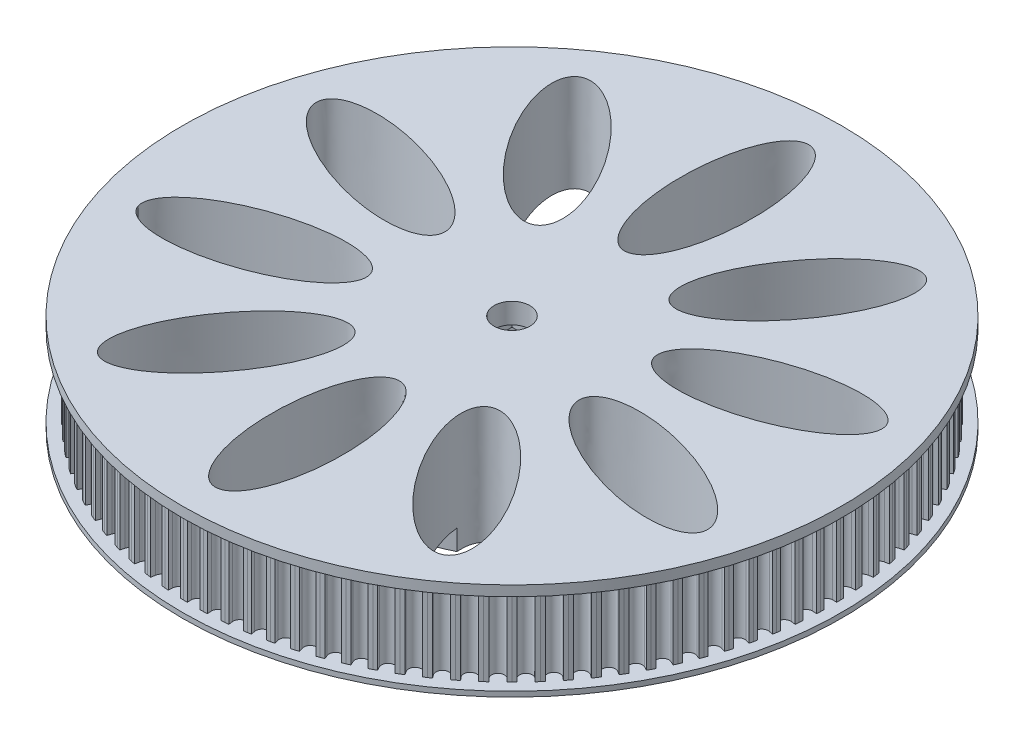
SolidWorks part; units mm, degrees
ref_plane "Front Plane" through (0, 0, 0) normal (0, 0, 1) x (1, 0, 0)
ref_plane "Top Plane" through (0, 0, 0) normal (0, 1, 0) x (1, 0, 0)
ref_plane "Right Plane" through (0, 0, 0) normal (1, 0, 0) x (0, 0, -1)
sketch "Sketch1" plane through (0, 0, 0) normal (0, 1, 0) x (1, 0, 0)
  circle A0 centre (0, 0) radius 32.2169
  circle A1 centre (0, 0) radius 8.55
  ellipse E0 centre (0, 20) end of major axis (0, 11) minor radius 3.5
  ellipse E1 centre (11.7557, 16.1803) end of major axis (6.4656, 8.8992) minor radius 3.5
  ellipse E2 centre (19.0211, 6.1803) end of major axis (27.5806, 8.9615) minor radius 3.5
  ellipse E3 centre (19.0211, -6.1803) end of major axis (10.4616, -3.3992) minor radius 3.5
  ellipse E4 centre (11.7557, -16.1803) end of major axis (17.0458, -23.4615) minor radius 3.5
  ellipse E5 centre (0, -20) end of major axis (0, -11) minor radius 3.5
  ellipse E6 centre (-11.7557, -16.1803) end of major axis (-6.4656, -8.8992) minor radius 3.5
  ellipse E7 centre (-19.0211, -6.1803) end of major axis (-27.5806, -8.9615) minor radius 3.5
  ellipse E8 centre (-19.0211, 6.1803) end of major axis (-27.5806, 8.9615) minor radius 3.5
  ellipse E9 centre (-11.7557, 16.1803) end of major axis (-17.0458, 23.4615) minor radius 3.5
  point P66 (0, 0)
  dimension "D1" = 64.4338
  dimension "D2" = 17.1
  dimension "D3" = 20
  dimension "D4" = 7
  dimension "D5" = 18
  dimension "D6" = 10
extrude "Boss-Extrude1" add sketch "Sketch1" along normal blind 11.5
sketch "Sketch2" plane through (0, 11.5, 0) normal (0, 1, 0) x (1, 0, 0)
  circle A0 centre (0, 0) radius 8.55
  circle A1 centre (0, 0) radius 8.55 construction
  circle A2 centre (0, 0) radius 1.75
  dimension "D1" = 3.5
extrude "Boss-Extrude2" add sketch "Sketch2" against normal blind 2
sketch "Sketch3" plane through (0, 9.5, 0) normal (0, -1, 0) x (-1, 0, 0)
  line L1 (6.0458, 6.0458) -> (-6.0458, 6.0458)
  line L2 (6.0458, 6.0458) -> (6.0458, -6.0458)
  line L3 (6.0458, -6.0458) -> (-6.0458, -6.0458)
  line L4 (-6.0458, 6.0458) -> (-6.0458, -6.0458)
  line L5 (6.0458, 6.0458) -> (-6.0458, -6.0458) construction
  line L6 (6.0458, -6.0458) -> (-6.0458, 6.0458) construction
  circle A0 centre (0, 0) radius 8.55 construction
  circle A1 centre (0, 0) radius 8.55 construction
  circle A2 centre (0, 0) radius 8.55
  point P0 (0, 0)
  circle M6 centre (0, 0) radius 8.55
extrude "Boss-Extrude3" add sketch "Sketch3" along normal blind 5 contours L3 M6 | L2 M6 | L4 M6 | L1 M6 region at (-7.0612, 9.5, 0) region at (0, 9.5, -7.0612) region at (7.0612, 9.5, 0) region at (0, 9.5, 7.0612)
sketch "Sketch4" plane through (0, 0, 0) normal (0, -1, 0) x (-1, 0, 0)
  circle A0 centre (0, 0) radius 12.55
  circle A1 centre (0, 0) radius 32.2169
  circle A2 centre (0, 0) radius 32.2169 construction
  arc A3 (-6.0458, 6.0458) -> (-6.0458, -6.0458) centre (0, 0) ccw construction
  dimension "D1" = 4
extrude "Cut-Extrude1" cut sketch "Sketch4" against normal blind 2 contours A1 | A0
sketch "Sketch5" plane through (0, 11.5, 0) normal (0, 1, 0) x (1, 0, 0)
  line L0 (0.63, 31.1169) -> (2, 31.1169)
  line L1 (-2, 31.1169) -> (-0.63, 31.1169)
  line L2 (-2, 31.1169) -> (-2, 34.1169)
  line L3 (-2, 34.1169) -> (2, 34.1169)
  line L4 (2, 31.1169) -> (2, 34.1169)
  line L5 (-0.63, 30.7169) -> (-0.63, 31.1169)
  line L6 (0.63, 30.7169) -> (0.63, 31.1169)
  arc A1 (-0.63, 30.7169) -> (0.63, 30.7169) centre (0, 30.7169) ccw
  point P12 (0, 34.1169)
  circle M9 centre (0, 0) radius 32.2169
  dimension "D2" = 1.26
  dimension "D3" = 4
  dimension "D1" = 30.7169
  dimension "D4" = 0.4
  dimension "D5" = 3
extrude "Cut-Extrude2" cut sketch "Sketch5" against normal blind 8 from offset 1 contours L5 A1 L6 L0 L4 L2 L1 M9 | L4 L3 L2 M9 region at (0, 11.5, -31.45) region at (0, 11.5, -33.1565) offset against normal yes
pattern_circular "CirPattern1" count 100 over 360 about axis through (0, 9.5, 0) along (0, 1, 0) of "Cut-Extrude2" reverse direction yes
equation "\"pitch\"= 1.93"
equation "\"amount_of_teeth\"= 100"
equation "\"pitch_diameter\"= ( \"pitch\" * \"amount_of_teeth\" ) / pi"
equation "\"D1@Sketch1\"=\"pitch_diameter\"+3"
equation "\"D1@CirPattern1\"=\"amount_of_teeth\""
equation "\"D1@Sketch5\"=\"pitch_diameter\"/2"
